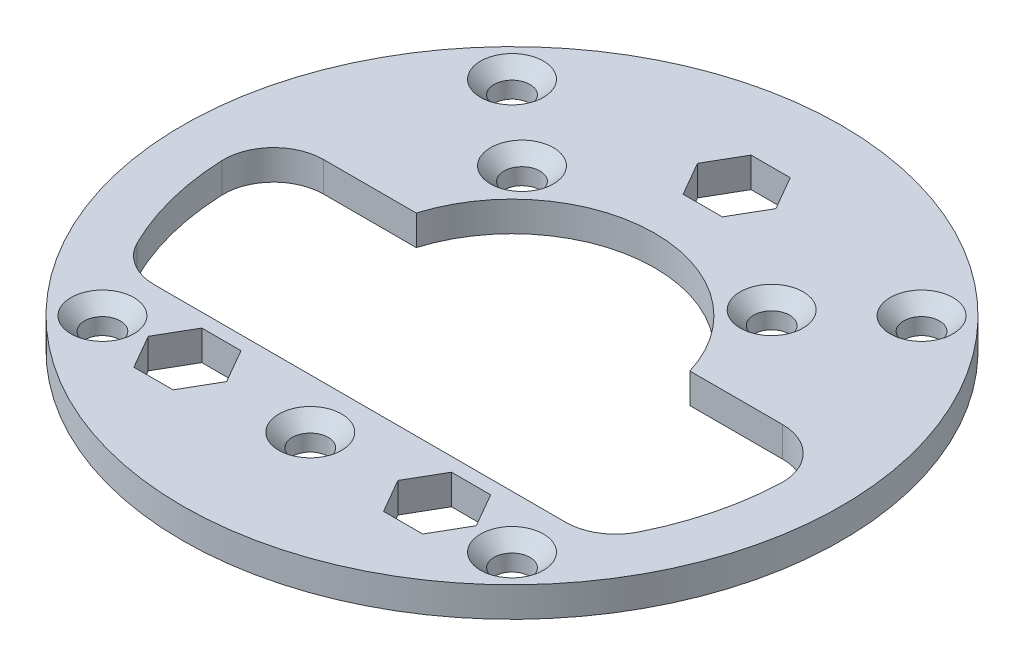
SolidWorks part; units mm, degrees
material "PEI"
ref_plane "Front Plane" through (0, 0, 0) normal (0, 0, 1) x (1, 0, 0)
ref_plane "Top Plane" through (0, 0, 0) normal (0, 1, 0) x (1, 0, 0)
ref_plane "Right Plane" through (0, 0, 0) normal (1, 0, 0) x (0, 0, -1)
sketch "Sketch1" plane through (0, 0, 0) normal (0, 1, 0) x (1, 0, 0)
  circle A0 centre (0, 0) radius 33
  circle A1 centre (0, 0) radius 28
  dimension "D1" = 66
  dimension "D2" = 5
extrude "Boss-Extrude1" add sketch "Sketch1" along normal blind 3
sketch "Sketch2" plane through (0, 3, 0) normal (0, 1, 0) x (1, 0, 0)
  line L0 (-23.5, -15.2233) -> (23.5, -15.2233)
  line L1 (-27.6968, 4.1095) -> (-13.6968, 4.1095)
  line L2 (0, 0) -> (7.7557, 0) construction
  line L3 (13.6968, 4.1095) -> (27.6968, 4.1095)
  line L4 (-20.5061, 20.5061) -> (0, 0) construction
  line L5 (-12.5, 13.5) -> (12.5, 13.5) construction
  circle A0 centre (0, 22.5) radius 2.25 construction
  circle A1 centre (-12.5, -20) radius 2.25 construction
  circle A2 centre (12.5, -20) radius 2.25 construction
  circle A4 centre (-12.5, 13.5) radius 1.5
  circle A6 centre (0, 0) radius 28 construction
  arc A8 (-13.6968, 4.1095) -> (13.6968, 4.1095) centre (0, 0) cw
  arc A9 (27.6968, 4.1095) -> (-27.6968, 4.1095) centre (0, 0) ccw
  arc A10 (23.5, -15.2233) -> (-23.5, -15.2233) centre (0, 0) cw
  circle A11 centre (12.5, 13.5) radius 1.5
  circle A12 centre (0, 0) radius 29 construction
  circle A13 centre (0, 0) radius 33 construction
  circle A14 centre (-20.5061, 20.5061) radius 1.75 construction
  circle A15 centre (20.5061, 20.5061) radius 1.75 construction
  circle A16 centre (20.5061, -20.5061) radius 1.75 construction
  circle A17 centre (-20.5061, -20.5061) radius 1.75 construction
  circle A18 centre (0, -20.2) radius 1.5
  point P15 (0, 13.5)
  point P19 (0, 0)
  point P44 (0, 0)
  circle M2 centre (0, 0) radius 28
  dimension "D5" = 4.5
  dimension "D6" = 4.5
  dimension "D7" = 4.5
  dimension "D12" = 14.3
  dimension "D16" = 3.5
  dimension "D11" = 3
  dimension "D1" = 25
  dimension "D2" = 12.5
  dimension "D3" = 22.5
  dimension "D4" = 20
  dimension "D14" = 4
  dimension "D15" = 135
  dimension "D8" = 14
  dimension "D9" = 14
  dimension "D10" = 47
  dimension "D18" = 25
  dimension "D19" = 20.2
  dimension "D13" = 13.5
  dimension "D17" = 4
extrude "Saliente-Extruir1" add sketch "Sketch2" against normal up to surface (3 mm away) contours L1 A8 L3 M2 | L0 M2 region at (0, 3, 15.7104) region at (0, 3, -15.6634) up to face at (0, 0, 33)
sketch "Croquis1" plane through (0, 3, 0) normal (0, 1, 0) x (1, 0, 0)
  line L1 (-8.574, -20) -> (-10.537, -16.6)
  line L2 (-10.537, -16.6) -> (-14.463, -16.6)
  line L3 (-14.463, -16.6) -> (-16.426, -20)
  line L4 (-16.426, -20) -> (-14.463, -23.4)
  line L5 (-14.463, -23.4) -> (-10.537, -23.4)
  line L6 (-10.537, -23.4) -> (-8.574, -20)
  line L7 (16.426, -20) -> (14.463, -16.6)
  line L8 (14.463, -16.6) -> (10.537, -16.6)
  line L9 (10.537, -16.6) -> (8.574, -20)
  line L10 (8.574, -20) -> (10.537, -23.4)
  line L11 (10.537, -23.4) -> (14.463, -23.4)
  line L12 (14.463, -23.4) -> (16.426, -20)
  line L13 (3.926, 22.5) -> (1.963, 25.9)
  line L14 (1.963, 25.9) -> (-1.963, 25.9)
  line L15 (-1.963, 25.9) -> (-3.926, 22.5)
  line L16 (-3.926, 22.5) -> (-1.963, 19.1)
  line L17 (-1.963, 19.1) -> (1.963, 19.1)
  line L18 (1.963, 19.1) -> (3.926, 22.5)
  circle A0 centre (-20.5061, 20.5061) radius 1.75 construction
  circle A1 centre (-20.5061, 20.5061) radius 1.75
  circle A4 centre (20.5061, 20.5061) radius 1.75 construction
  circle A5 centre (20.5061, 20.5061) radius 1.75
  circle A6 centre (-12.5, -20) radius 3.4 construction
  circle A7 centre (12.5, -20) radius 3.4 construction
  circle A8 centre (0, 22.5) radius 3.4 construction
  circle A16 centre (-20.5061, -20.5061) radius 1.75 construction
  circle A17 centre (-20.5061, -20.5061) radius 1.75
  circle A18 centre (20.5061, -20.5061) radius 1.75 construction
  circle A19 centre (20.5061, -20.5061) radius 1.75
  dimension "D1" = 6.8
  dimension "D2" = 6.8
  dimension "D3" = 6.8
extrude "Cortar-Extruir1" cut sketch "Croquis1" against normal up to next
hole_wizard "CSK for M3 Flat Head Machine Screw1" positions "Sketch4" profile "Sketch5" countersink size "M3" standard "ANSI Metric" end condition through all
sketch "Sketch4" plane through (0, 3, 0) normal (0, 1, 0) x (1, 0, 0)
  point P0 (-20.5061, 20.5061)
  point P3 (20.5061, 20.5061)
  point P6 (20.5061, -20.5061)
  point P9 (-20.5061, -20.5061)
sketch "Sketch5" plane through (-20.5061, 3, -20.5061) normal (1, 0, 0) x (0, 0, 1)
  line L0 (0, 0) -> (0, 3)
  line L1 (0, 3) -> (1.8, 3)
  line L2 (1.8, 3) -> (1.8, 1.35)
  line L3 (1.8, 1.35) -> (3.15, 0)
  line L5 (3.15, 0) -> (0, 0)
  line L6 (-1.8, 1.35) -> (-3.15, 0) construction
  line L11 (0, -6.35) -> (0, 107.95) construction
  dimension "Thru Hole Dia." = 3.6
  dimension "Thru Hole Depth" = 3
  dimension "Near C'Sink Dia." = 6.3
  dimension "Near C'Sink Angle" = 90
hole_wizard "CSK for M3 Flat Head Machine Screw2" positions "Sketch6" profile "Sketch7" countersink size "M3" standard "ANSI Metric" end condition through all
sketch "Sketch6" plane through (0, 3, 0) normal (0, 1, 0) x (1, 0, 0)
  point P12 (-12.5, 13.5)
  point P15 (12.5, 13.5)
  point P18 (0, -20.2)
sketch "Sketch7" plane through (-12.5, 3, -13.5) normal (1, 0, 0) x (0, 0, 1)
  line L0 (0, 0) -> (0, 3)
  line L1 (0, 3) -> (1.8, 3)
  line L2 (1.8, 3) -> (1.8, 1.35)
  line L3 (1.8, 1.35) -> (3.15, 0)
  line L5 (3.15, 0) -> (0, 0)
  line L6 (-1.8, 1.35) -> (-3.15, 0) construction
  line L11 (0, -6.35) -> (0, 107.95) construction
  dimension "Thru Hole Dia." = 3.6
  dimension "Thru Hole Depth" = 3
  dimension "Near C'Sink Dia." = 6.3
  dimension "Near C'Sink Angle" = 90
fillet "Fillet1" radius 5 4 edges at (-27.6968, 1.5, -4.1095) (27.6968, 1.5, -4.1095) (23.5, 1.5, 15.2233) (-23.5, 1.5, 15.2233)
equation "\"D2@Sketch2\"=\"D1@Sketch2\"/2"
equation "\"D6@Sketch2\"=\"D5@Sketch2\""
equation "\"D7@Sketch2\"=\"D6@Sketch2\""
equation "\"D2@Croquis1\"=\"D3@Croquis1\""
equation "\"D1@Croquis1\"=\"D3@Croquis1\""
